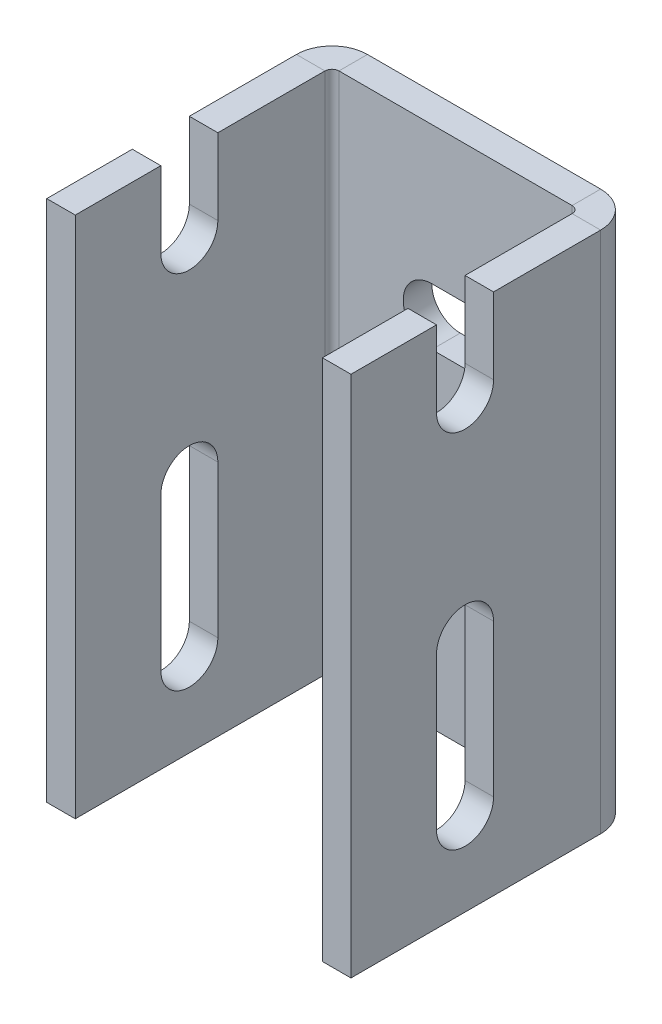
SolidWorks part; units mm, degrees
note: The reader was unsure of these and kept them because the rebuilt part matched: thickness of "Base-Flange1", "Edge-Flange1", "Sheet-Metal1", "Sheet-Metal2", "Sheet-Metal3", "Sheet-Metal4"; flange length of "Edge-Flange1".
ref_plane "Front Plane" through (0, 0, 0) normal (0, 0, 1) x (1, 0, 0)
ref_plane "Top Plane" through (0, 0, 0) normal (0, 1, 0) x (1, 0, 0)
ref_plane "Right Plane" through (0, 0, 0) normal (1, 0, 0) x (0, 0, -1)
sketch "Sketch1" plane through (0, 0, 0) normal (0, 0, 1) x (1, 0, 0)
  line L1 (0, 0) -> (32, 0)
  line L2 (0, 0) -> (0, 55)
  line L3 (0, 55) -> (32, 55)
  line L4 (32, 0) -> (32, 55)
  dimension "D1" = 32
  dimension "D2" = 55
base flange "Base-Flange1" sketch "Sketch1" thickness 3 reverse thickness direction no parameters "D1"=0.7366
edge flange "Edge-Flange1" sketch "Sketch10" flange profiles "Sketch10", "Sketch11" flange angle 90 flange length 30 flange position material inside bend radius 0.7366 thickness 3 relief rectangular parameters "D6"=10, "D8"=1
sketch "Sketch10" plane through (32, 0, 0) normal (1, 0, 0) x (0, 1, 0)
  line L0 (0, 0) -> (55, 0) construction
  line L1 (0, 0) -> (55, 0)
  line L2 (0, 0) -> (0, 27)
  line L3 (0, 27) -> (55, 27)
  line L4 (55, 27) -> (55, 0)
sketch "Sketch11" plane through (0, 0, 0) normal (-1, 0, 0) x (0, -1, 0)
  line L0 (-55, 0) -> (0, 0) construction
  line L1 (-55, 0) -> (0, 0)
  line L2 (-55, 0) -> (-55, 27)
  line L3 (-55, 27) -> (0, 27)
  line L4 (0, 27) -> (0, 0)
bend "EdgeBend1" bend radius 0.7366 bend angle 90 parameters "D5"=1
bend "EdgeBend2" bend radius 0.7366 bend angle 90 parameters "D5"=2
sketch "Sketch12" plane through (0, 0, 0) normal (0, 0, 1) x (1, 0, 0)
  line L0 (16, 55) -> (16, 0) construction
  line L1 (28.2634, 55) -> (3.7366, 55) construction
  line L2 (3.7366, 0) -> (28.2634, 0) construction
  line L3 (13.5, 37.5) -> (18.5, 37.5) construction
  line L4 (13.5, 40.5) -> (18.5, 40.5)
  line L5 (13.5, 34.5) -> (18.5, 34.5)
  line L6 (13.5, 17.5) -> (18.5, 17.5) construction
  line L7 (13.5, 20.5) -> (18.5, 20.5)
  line L8 (13.5, 14.5) -> (18.5, 14.5)
  arc A0 (13.5, 40.5) -> (13.5, 34.5) centre (13.5, 37.5) ccw
  arc A1 (18.5, 34.5) -> (18.5, 40.5) centre (18.5, 37.5) ccw
  arc A2 (13.5, 20.5) -> (13.5, 14.5) centre (13.5, 17.5) ccw
  arc A3 (18.5, 14.5) -> (18.5, 20.5) centre (18.5, 17.5) ccw
  point P8 (16, 37.5)
  point P14 (16, 17.5)
  dimension "D1" = 5
  dimension "D2" = 6
  dimension "D3" = 17.5
  dimension "D4" = 20
extrude "Cut-Extrude1" cut sketch "Sketch12" against normal through all normal cut yes
sketch "Sketch13" plane through (32, 0, 0) normal (1, 0, 0) x (0, 0, -1)
  line L0 (-15, 55) -> (-15, 47) construction
  line L1 (-0.7366, 55) -> (-27, 55) construction
  line L2 (-12, 55) -> (-12, 47)
  line L3 (-18, 55) -> (-18, 47)
  line L4 (-15, 25) -> (-15, 9) construction
  line L5 (-12, 25) -> (-12, 9)
  line L6 (-18, 25) -> (-18, 9)
  line L7 (-27, 55) -> (-27, 0) construction
  line L8 (-27, 0) -> (-0.7366, 0) construction
  arc A0 (-12, 55) -> (-18, 55) centre (-15, 55) ccw
  arc A1 (-18, 47) -> (-12, 47) centre (-15, 47) ccw
  arc A2 (-12, 25) -> (-18, 25) centre (-15, 25) ccw
  arc A3 (-18, 9) -> (-12, 9) centre (-15, 9) ccw
  point P4 (-15, 51)
  point P9 (-15, 17)
  dimension "D6" = 9
  dimension "D1" = 6
  dimension "D2" = 8
  dimension "D3" = 9
  dimension "D4" = 9
  dimension "D5" = 16
extrude "Cut-Extrude2" cut sketch "Sketch13" against normal through all normal cut yes
sketch "Bend-Lines1" [suppressed] plane through (0, 0, 0) normal (0, 1, 0) x (1, 0, 0)
sketch "Bounding-Box1" [suppressed] plane through (0, 0, 0) normal (0, 1, 0) x (1, 0, 0)
sheet metal parameters "Sheet-Metal1" thickness 3 parameters "D1"=0.7366
flat pattern "Flat-Pattern1" [suppressed]
sketch "Bend-Lines2" plane through (0, 0, 0) normal (0, 1, 0) x (1, 0, 0)
sketch3d "Bounding-Box2" [suppressed]
  line L0 (-30, 60, 0) -> (-30, 0, 0) construction
  line L1 (0, 60, 0) -> (0, 0, 0) construction
  line L2 (-30, 60, 0) -> (0, 60, 0) construction
  line L3 (-30, 0, 0) -> (0, 0, 0) construction
sheet metal parameters "Sheet-Metal2" thickness 3 parameters "D1"=0.7366, "D7"=2.5
flat pattern "Flat-Pattern1"
sketch "Bend-Lines2" plane through (0, 0, 0) normal (0, 0, 1) x (1, 0, 0)
  line L0 (1.6763, 60) -> (1.6763, 0) construction
  line L1 (28.3237, 0) -> (28.3237, 60) construction
  line L2 (1.6763, 60) -> (1.6763, 0) construction
  line L3 (28.3237, 0) -> (28.3237, 60) construction
sketch3d "Bounding-Box2" [suppressed]
  line L0 (-26.6473, 0, 0) -> (56.6473, 0, 0) construction
  line L1 (-26.6473, 60, 0) -> (56.6473, 60, 0) construction
  line L2 (-26.6473, 0, 0) -> (-26.6473, 60, 0) construction
  line L3 (56.6473, 0, 0) -> (56.6473, 60, 0) construction
bend of the flat pattern "Flatten-<EdgeBend1>1"
bend of the flat pattern "Flatten-<EdgeBend2>1"
sheet metal parameters "Sheet-Metal3" thickness 3 parameters "D1"=0.7366, "D7"=2.5
flat pattern "Flat-Pattern1"
sketch "Bend-Lines2" plane through (0, 0, 0) normal (0, 0, 1) x (1, 0, 0)
  line L0 (1.6763, 60) -> (1.6763, 0) construction
  line L1 (28.3237, 0) -> (28.3237, 60) construction
  line L2 (1.6763, 60) -> (1.6763, 0) construction
  line L3 (28.3237, 0) -> (28.3237, 60) construction
sketch3d "Bounding-Box2" [suppressed]
  line L0 (-26.6473, 0, 0) -> (56.6473, 0, 0) construction
  line L1 (-26.6473, 60, 0) -> (56.6473, 60, 0) construction
  line L2 (-26.6473, 0, 0) -> (-26.6473, 60, 0) construction
  line L3 (56.6473, 0, 0) -> (56.6473, 60, 0) construction
bend of the flat pattern "Flatten-<EdgeBend1>1"
bend of the flat pattern "Flatten-<EdgeBend2>1"
sheet metal parameters "Sheet-Metal4" thickness 3 parameters "D1"=0.7366, "D7"=2.5
flat pattern "Flat-Pattern1"
sketch "Bend-Lines2" plane through (0, 0, 0) normal (0, 0, 1) x (1, 0, 0)
  line L0 (1.98, 55) -> (1.98, 0) construction
  line L1 (30.02, 0) -> (30.02, 55) construction
  line L2 (1.98, 55) -> (1.98, 0) construction
  line L3 (30.02, 0) -> (30.02, 55) construction
sketch3d "Bounding-Box2" [suppressed]
  line L0 (-26.04, 0, 0) -> (58.04, 0, 0) construction
  line L1 (-26.04, 55, 0) -> (58.04, 55, 0) construction
  line L2 (-26.04, 0, 0) -> (-26.04, 55, 0) construction
  line L3 (58.04, 0, 0) -> (58.04, 55, 0) construction
bend of the flat pattern "Flatten-<EdgeBend1>1"
bend of the flat pattern "Flatten-<EdgeBend2>1"
